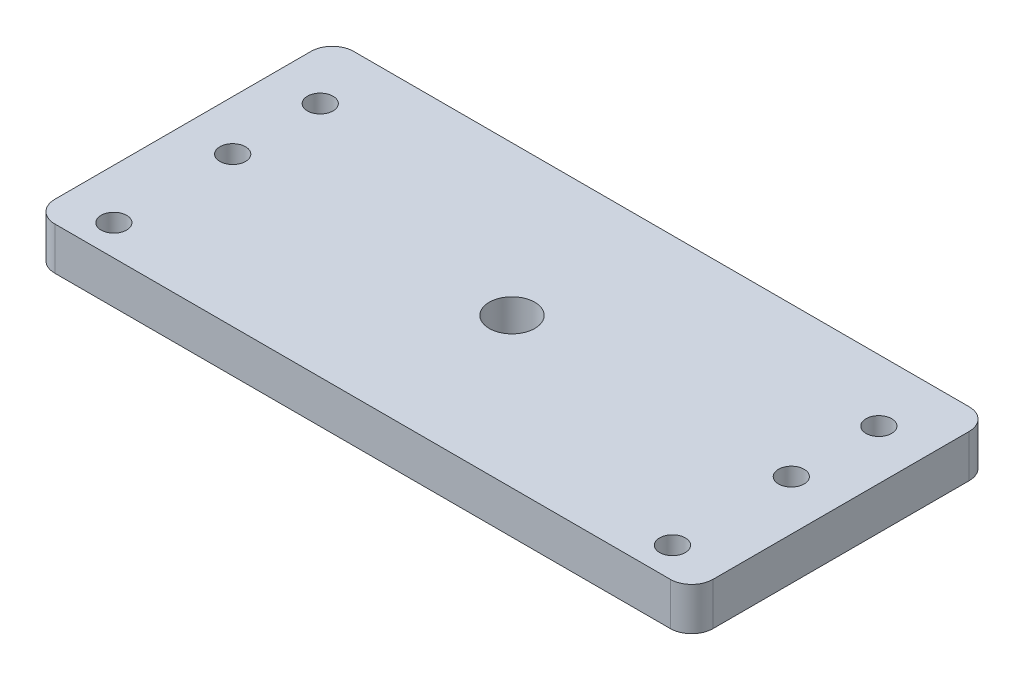
SolidWorks part; units mm, degrees
ref_plane "Płaszczyzna przednia" through (0, 0, 0) normal (0, 0, 1) x (1, 0, 0)
ref_plane "Płaszczyzna górna" through (0, 0, 0) normal (0, 1, 0) x (1, 0, 0)
ref_plane "Płaszczyzna prawa" through (0, 0, 0) normal (1, 0, 0) x (0, 0, -1)
sketch "Sketch2" plane through (0, 0, 0) normal (0, 1, 0) x (1, 0, 0)
  line L0 (-25.9967, 13.7153) -> (66.5033, 13.7153) construction
  line L1 (-25.9967, 34.7153) -> (66.5033, 34.7153)
  line L2 (-25.9967, 34.7153) -> (-25.9967, -7.2847)
  line L3 (-25.9967, -7.2847) -> (66.5033, -7.2847)
  line L4 (66.5033, 34.7153) -> (66.5033, -7.2847)
  line L5 (20.2533, 34.7153) -> (20.2533, -7.2847) construction
  circle A4 centre (20.2533, 13.7153) radius 3.2
  dimension "D6" = 6.4
extrude "Boss-Extrude1" add sketch "Sketch2" along normal blind 6
sketch "Sketch5" plane through (0, 0, 0) normal (0, -1, 0) x (-1, 0, 0)
  point P0 (-59.5033, 26.0153)
  point P3 (-59.5033, -2.9847)
  point P6 (18.9967, -2.9847)
  point P9 (18.9967, 26.0153)
hole_wizard "M3 Clearance Hole1" positions "Sketch5" profile "Sketch4" hole size "M3" standard "DIN"
sketch "Sketch4" plane through (59.5033, 0, -26.0153) normal (1, 0, 0) x (0, 0, -1)
  line L0 (0, 0) -> (0, 11.0815)
  line L1 (0, 11.0815) -> (1.8, 10)
  line L2 (1.8, 10) -> (1.8, 0)
  line L5 (1.8, 0) -> (0, 0)
  line L10 (0, 11.0815) -> (-1.8, 10) construction
  line L11 (0, -6.35) -> (0, 107.95) construction
  dimension "Hole Dia." = 3.6
  dimension "Hole Depth" = 10
  dimension "Drill Angle" = 118
sketch "Sketch7" plane through (0, 0, 0) normal (0, -1, 0) x (1, 0, 0)
  circle A0 centre (20.2533, -13.7153) radius 3.2 construction
  circle A1 centre (20.2533, -13.7153) radius 3.2
  circle A2 centre (20.2533, -13.7153) radius 7.2
  dimension "D1" = 4
extrude "Boss-Extrude2" add sketch "Sketch7" along normal blind 3
chamfer "Chamfer1" distance 3 angle 45 1 edges at (20.2533, 0, -6.5153)
fillet "Fillet1" radius 3 4 edges at (-25.9967, 3, -34.7153) (-25.9967, 3, 7.2847) (66.5033, 3, 7.2847) (66.5033, 3, -34.7153)
sketch "Sketch10" plane through (0, 0, 0) normal (0, -1, 0) x (-1, 0, 0)
  point P0 (-59.5033, 13.7153)
  point P2 (18.9967, 13.7153)
hole_wizard "CSK for M3 Hex Socket Countersunk Head Screw1" positions "Sketch10" profile "Sketch11" countersink size "M3" standard "DIN" end condition through all
sketch "Sketch11" plane through (59.5033, 0, -13.7153) normal (1, 0, 0) x (0, 0, -1)
  line L0 (0, 0) -> (0, 6)
  line L1 (0, 6) -> (1.8, 6)
  line L2 (1.8, 6) -> (1.8, 1.67)
  line L3 (1.8, 1.67) -> (3.47, 0)
  line L5 (3.47, 0) -> (0, 0)
  line L6 (-1.8, 1.67) -> (-3.47, 0) construction
  line L11 (0, -6.35) -> (0, 107.95) construction
  dimension "Thru Hole Dia." = 3.6
  dimension "Thru Hole Depth" = 6
  dimension "Near C'Sink Dia." = 6.94
  dimension "Near C'Sink Angle" = 90
